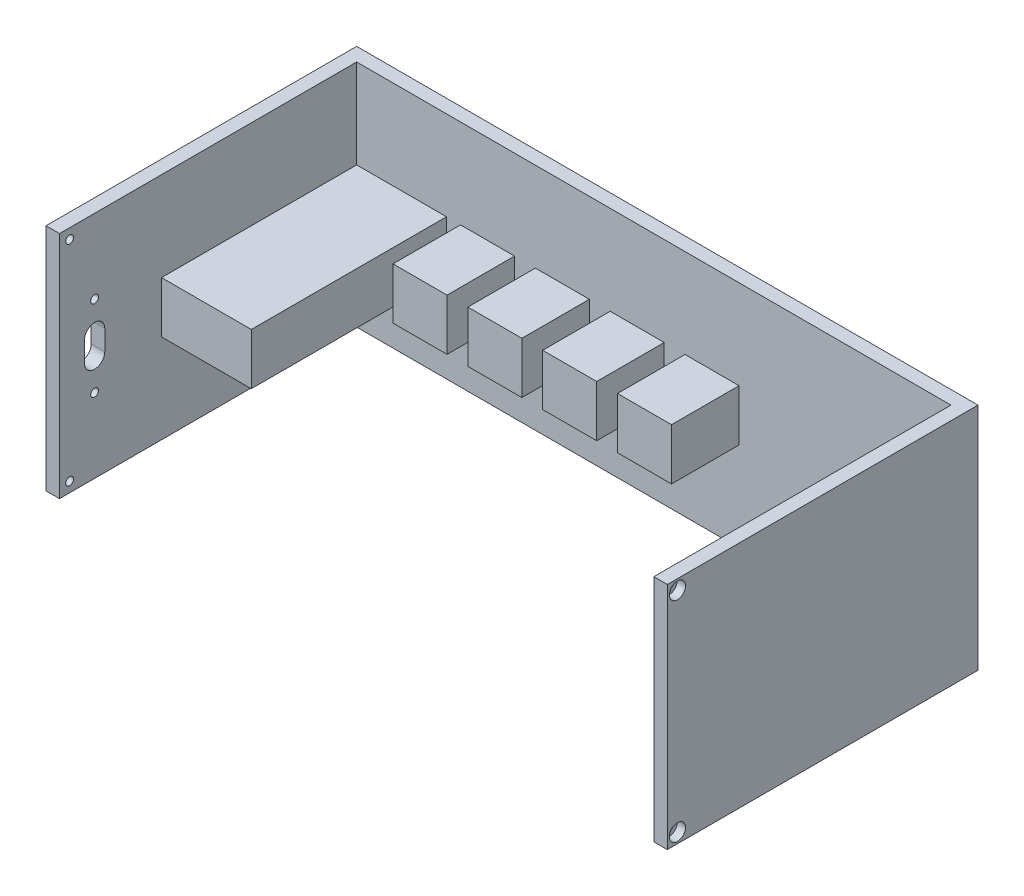
SolidWorks part; units mm, degrees
ref_plane "Front Plane" through (0, 0, 0) normal (1, 0, 0) x (0, 1, 0)
ref_plane "Top Plane" through (0, 0, 0) normal (0, 0, 1) x (0, 1, 0)
ref_plane "Right Plane" through (0, 0, 0) normal (0, 1, 0) x (-1, 0, 0)
sketch "Sketch1" plane through (0, 0, 0) normal (0, 0, 1) x (0, 1, 0)
  line L2 (-42.5, 94.3065) -> (-42.5, -115)
  line L3 (-42.5, -115) -> (42.5, -115)
  line L9 (-42.5, 94.3065) -> (-42.5, 115)
  line L10 (-42.5, 115) -> (42.5, 115)
  line L12 (42.5, 115) -> (42.5, 94.3065)
  line L13 (42.5, 94.3065) -> (42.5, -115)
  line L14 (-42.5, 115) -> (42.5, -115) construction
  line L15 (42.5, 115) -> (-42.5, -115) construction
  point P0 (0, 0)
  point P5 (-42.5, 94.3065)
  dimension "D1" = 230
  dimension "D2" = 85
extrude "Boss-Extrude1" add sketch "Sketch1" along normal blind 5
sketch "Sketch2" plane through (0, 0, 5) normal (0, 0, 1) x (1, 0, 0)
  line L0 (-115, 42.5) -> (-94.3065, 42.5) construction
  line L7 (-115, -42.5) -> (-110, -42.5)
  line L15 (-71.55, 9.5) -> (-51.55, 9.5)
  line L16 (-71.55, 9.5) -> (-71.55, -9.5)
  line L17 (-71.55, -9.5) -> (-51.55, -9.5)
  line L18 (-51.55, 9.5) -> (-51.55, -9.5)
  line L19 (-71.55, 9.5) -> (-51.55, -9.5) construction
  line L20 (-71.55, -9.5) -> (-51.55, 9.5) construction
  line L21 (-43.85, 9.5) -> (-23.85, 9.5)
  line L22 (-43.85, 9.5) -> (-43.85, -9.5)
  line L23 (-43.85, -9.5) -> (-23.85, -9.5)
  line L24 (-23.85, 9.5) -> (-23.85, -9.5)
  line L25 (-43.85, 9.5) -> (-23.85, -9.5) construction
  line L26 (-43.85, -9.5) -> (-23.85, 9.5) construction
  line L27 (-16.15, 9.5) -> (3.85, 9.5)
  line L28 (-16.15, 9.5) -> (-16.15, -9.5)
  line L29 (-16.15, -9.5) -> (3.85, -9.5)
  line L30 (3.85, 9.5) -> (3.85, -9.5)
  line L31 (-16.15, 9.5) -> (3.85, -9.5) construction
  line L32 (-16.15, -9.5) -> (3.85, 9.5) construction
  line L33 (11.55, 9.5) -> (31.55, 9.5)
  line L34 (11.55, 9.5) -> (11.55, -9.5)
  line L35 (11.55, -9.5) -> (31.55, -9.5)
  line L36 (31.55, 9.5) -> (31.55, -9.5)
  line L37 (11.55, 9.5) -> (31.55, -9.5) construction
  line L38 (11.55, -9.5) -> (31.55, 9.5) construction
  line L39 (-115, -42.5) -> (-115, 42.5)
  line L40 (-115, 42.5) -> (-110, 42.5)
  line L41 (-115, -42.5) -> (115, -42.5) construction
  line L42 (115, 42.5) -> (110, 42.5)
  line L43 (115, 42.5) -> (115, -42.5)
  line L44 (115, -42.5) -> (110, -42.5)
  line L45 (110, 42.5) -> (110, -42.5)
  line L46 (115, 42.5) -> (110, -42.5) construction
  line L47 (115, -42.5) -> (110, 42.5) construction
  line L48 (-23.85, 9.5) -> (-16.15, -9.5)
  line L49 (-110, -42.5) -> (-110, 42.5)
  line L50 (-115, -42.5) -> (-110, 42.5) construction
  line L51 (-115, 42.5) -> (-110, -42.5) construction
  line L52 (-110, 9.5) -> (-76.75, 9.5)
  line L53 (-110, 9.5) -> (-110, -9.5)
  line L54 (-110, -9.5) -> (-76.75, -9.5)
  line L55 (-76.75, 9.5) -> (-76.75, -9.5)
  line L56 (-110, 9.5) -> (-76.75, -9.5) construction
  line L57 (-110, -9.5) -> (-76.75, 9.5) construction
  point P4 (-112.5, 0)
  point P12 (112.5, 0)
  point P16 (-61.55, 0)
  point P21 (-33.85, 0)
  point P26 (-6.15, 0)
  point P31 (21.55, 0)
  point P36 (-20, 0)
  point P40 (-93.375, 0)
  dimension "D1" = 5
  dimension "D2" = 20
  dimension "D3" = 19
  dimension "D4" = 7.7
  dimension "D5" = 7.7
  dimension "D6" = 7.7
  dimension "D7" = 5
  dimension "D8" = 20
  dimension "D9" = 5.2
extrude "Boss-Extrude3" add sketch "Sketch2" along normal blind 110 contours L42 L45 L44 L43 | L40 L49 L7 L39
extrude "Boss-Extrude4" add sketch "Sketch2<3>" along normal blind 25 contours L18 L15 L16 L17 | L24 L21 L22 L23 | L30 L27 L28 L29 | L36 L33 L34 L35 region at (-61.55, 0, 5) region at (-6.15, 0, 5) region at (-33.85, 0, 5) region at (21.55, 0, 5)
sketch "Sketch2<3>" plane through (0, 0, 5) normal (0, 0, 1) x (1, 0, 0) same geometry as "Sketch2"
sketch "Sketch3" plane through (-115, 0, 0) normal (-1, 0, 0) x (0, -1, 0)
  line L0 (-3.75, 102) -> (3.75, 102) construction
  line L1 (-3.75, 105.75) -> (3.75, 105.75)
  line L2 (-3.75, 98.25) -> (3.75, 98.25)
  line L4 (-42.5, 0) -> (42.5, 0) construction
  arc A0 (-3.75, 105.75) -> (-3.75, 98.25) centre (-3.75, 102) ccw
  arc A1 (3.75, 98.25) -> (3.75, 105.75) centre (3.75, 102) ccw
  circle A2 centre (-15, 102) radius 1.45
  circle A3 centre (15, 102) radius 1.45
  point P2 (0, 102)
  point P9 (-7.5, 102)
  point P10 (7.5, 102)
  point P16 (-16.45, 102)
  dimension "D2" = 3.75
  dimension "D4" = 2.9
  dimension "D5" = 15
  dimension "D1" = 102
  dimension "D3" = 15
  dimension "D6" = 15
extrude "Cut-Extrude1" cut sketch "Sketch3" against normal up to surface (5 mm away) up to face at (-110, 0, 60)
sketch "Sketch4" plane through (0, 0, 5) normal (0, 0, 1) x (1, 0, 0)
  line L0 (-51.55, 9.5) -> (-43.85, -9.5) construction
  line L1 (2.8128, -9.5) -> (11.55, 9.5) construction
  circle A0 centre (-47.7, 0) radius 1.45
  circle A1 centre (7.1814, 0) radius 1.45
  dimension "D1" = 2.9
extrude "Cut-Extrude2" cut sketch "Sketch4" against normal up to surface (5 mm away) contours A0 | A1 up to face at (0, 0, 0)
sketch "Sketch5" plane through (115, 0, 0) normal (1, 0, 0) x (0, 1, 0)
  line L0 (42.5, 115) -> (-42.5, 115) construction
  line L1 (-42.5, 115) -> (-42.5, 0) construction
  line L2 (42.5, 115) -> (42.5, 0) construction
  circle A0 centre (-38.75, 111.25) radius 3
  circle A1 centre (38.75, 111.25) radius 3
  circle A2 centre (-38.75, 111.25) radius 1.45
  circle A3 centre (38.75, 111.25) radius 1.45
  dimension "D1" = 6
  dimension "D5" = 2.9
  dimension "D2" = 3.75
  dimension "D3" = 3.75
  dimension "D4" = 3.75
extrude "Cut-Extrude3" cut sketch "Sketch5" against normal blind 3.1
extrude "Cut-Extrude4" cut sketch "Sketch5<2>" against normal up to surface (5 mm away) contours A2 | A3 region at (115, -38.75, 111.25) region at (115, 38.75, 111.25) up to face at (110, 0, 60)
sketch "Sketch5<2>" plane through (115, 0, 0) normal (1, 0, 0) x (0, 1, 0) same geometry as "Sketch5"
sketch "Sketch6" plane through (-115, 0, 0) normal (-1, 0, 0) x (0, -1, 0)
  line L0 (42.5, 115) -> (-42.5, 115) construction
  line L1 (-42.5, 115) -> (-42.5, 0) construction
  line L2 (42.5, 115) -> (42.5, 0) construction
  circle A0 centre (-38.75, 111.25) radius 1.45
  circle A1 centre (38.75, 111.25) radius 1.45
  point P10 (0, 0)
  dimension "D1" = 2.9
  dimension "D2" = 2.9
  dimension "D3" = 3.75
  dimension "D4" = 3.75
  dimension "D5" = 3.75
extrude "Cut-Extrude5" cut sketch "Sketch6" against normal up to surface (5 mm away) up to face at (-110, -15, 103.45)
extrude "Boss-Extrude6" add sketch "Sketch2<7>" along normal blind 72.25 contours L54 L55 L52 L53
sketch "Sketch2<7>" plane through (0, 0, 5) normal (0, 0, 1) x (1, 0, 0) same geometry as "Sketch2"
